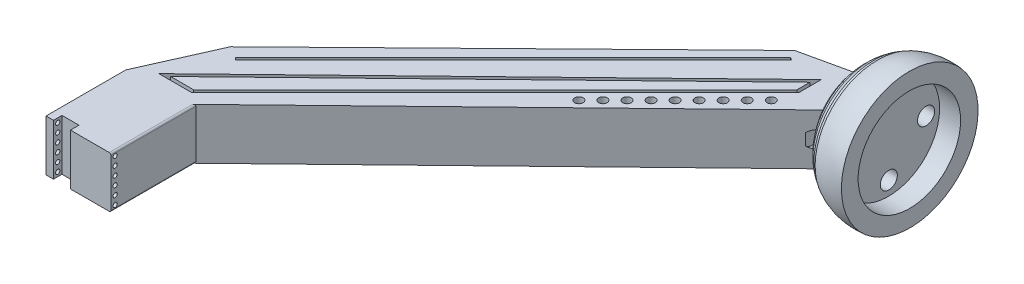
SolidWorks part; units mm, degrees
material "1060 Alloy"
ref_plane "Front Plane" through (0, 0, 0) normal (0, 0, 1) x (1, 0, 0)
ref_plane "Top Plane" through (0, 0, 0) normal (0, 1, 0) x (1, 0, 0)
ref_plane "Right Plane" through (0, 0, 0) normal (1, 0, 0) x (0, 0, -1)
sketch "Sketch1" plane through (0, 0, 0) normal (0, 1, 0) x (1, 0, 0)
  line L0 (-359.7122, -316.6922) -> (-359.7122, -189.6922)
  line L1 (-359.7122, -189.6922) -> (185.2241, 342.9318)
  line L2 (185.2241, 342.9318) -> (213.5101, 342.8041)
  line L3 (213.5101, 342.8041) -> (213.5101, 304.1714)
  line L4 (213.5101, 304.1714) -> (217.8609, 276.2217)
  line L5 (217.8609, 276.2217) -> (-262.803, -189.6922)
  line L6 (-262.803, -189.6922) -> (-262.803, -316.6922)
  line L7 (-262.803, -316.6922) -> (-359.7122, -316.6922)
  dimension "D1" = 762
  dimension "D2" = 127
extrude "Boss-Extrude1" add sketch "Sketch1" along normal blind 76.2
ref_plane "Plane1" through (1.4653, 0, -324.4575) normal (0.0045, 0, -1) x (-1, 0, -0.0045)
sketch "Sketch2" plane through (1.4653, 0, -324.4575) normal (0.0045, 0, -1) x (-1, 0, -0.0045)
  line L0 (-211.9599, 38.1) -> (-386.4485, 38.1) construction
  line L1 (-211.9599, 76.2) -> (-211.9599, 0) construction
sketch "Sketch3" plane through (1.4653, 0, -324.4575) normal (0.0045, 0, -1) x (-1, 0, -0.0045)
  line L0 (-289.3075, 139.7) -> (-289.3075, 38.1)
  line L1 (-211.9599, 38.1) -> (-386.4485, 38.1) construction
  line L2 (-289.3075, 38.1) -> (-185.548, 38.1)
  spline S0 degree 2 poles (-185.548, 38.1) (-211.3385, 147.1791) (-289.3075, 139.7) knots 0 0 0 1 1 1
  dimension "D1" = 101.6
revolve "Revolve1" add sketch "Sketch3" angle 360 about L0 region at (248.1956, 82.1116, -323.3432)
fillet "Fillet1" radius 20.32 1 edges at (192.4111, 35.4411, -342.8994)
fillet "Fillet2" radius 20.32 1 edges at (-359.7122, 38.1, 189.6922)
ref_plane "Plane4" through (308.6083, 0, 1.3937) normal (1, 0, 0.0045) x (0.0045, 0, -1)
sketch "Sketch4" plane through (308.6083, 0, 1.3937) normal (1, 0, 0.0045) x (0.0045, 0, -1)
  circle A0 centre (323.8985, 38.1) radius 76.2
  dimension "D1" = 152.4
extrude "Cut-Extrude1" cut sketch "Sketch4" against normal blind 50.8
ref_plane "Plane5" through (199.644, 0, 0) normal (1, 0, 0) x (0, 0, -1)
sketch "Sketch5" plane through (199.644, 0, 0) normal (1, 0, 0) x (0, 0, -1)
  circle A0 centre (325.0415, 93.4999) radius 12.7
  dimension "D1" = 25.4
extrude "Cut-Extrude2" cut sketch "Sketch5" along normal through all
sketch "Sketch6" plane through (199.644, 0, 0) normal (1, 0, 0) x (0, 0, -1)
  circle A0 centre (323.3573, 38.1) radius 55.4255
  circle A1 centre (378.7828, 38.1) radius 12.7
  circle A2 centre (323.3573, -17.3255) radius 12.7
  circle A3 centre (267.9318, 38.1) radius 12.7
  circle A4 centre (325.0415, 93.4999) radius 12.7 construction
  dimension "D1" = 110.8509
extrude "Cut-Extrude3" cut sketch "Sketch6" along normal through all contours A0 A1 | A0 A3 | A0 A3 | A1 | A2 region at (199.644, 38.1, -383.9023) region at (199.644, 38.1, -273.5754) region at (199.644, 38.1, -262.8123)
ref_plane "Plane6" through (0, 76.2, 0) normal (0, 1, 0) x (1, 0, 0)
sketch "Sketch7" plane through (0, 76.2, 0) normal (0, 1, 0) x (1, 0, 0)
  line L0 (-262.803, -189.6922) -> (212.8674, 271.3814) construction
  circle A0 centre (18.0584, 101.6525) radius 6.35
  circle A1 centre (36.0189, 119.613) radius 6.35
  circle A2 centre (53.9794, 137.5736) radius 6.35
  circle A3 centre (71.9399, 155.5341) radius 6.35
  circle A4 centre (89.9004, 173.4946) radius 6.35
  circle A5 centre (107.861, 191.4551) radius 6.35
  circle A6 centre (125.8215, 209.4156) radius 6.35
  circle A7 centre (143.782, 227.3761) radius 6.35
  circle A8 centre (161.7425, 245.3366) radius 6.35
  dimension "D1" = 12.7
  dimension "D2" = 13.716
  dimension "D3" = 9
extrude "Cut-Extrude5" cut sketch "Sketch7" against normal through all
ref_plane "Plane7" through (0, 76.2, 0) normal (0, 1, 0) x (1, 0, 0)
sketch "Sketch8" plane through (0, 76.2, 0) normal (0, 1, 0) x (1, 0, 0)
  line L0 (-348.5362, -316.6922) -> (-348.5362, -303.9922)
  line L1 (-359.7122, -316.6922) -> (-262.803, -316.6922) construction
  line L2 (-348.5362, -303.9922) -> (-323.1362, -303.9922)
  line L3 (-323.1362, -303.9922) -> (-323.1362, -316.6922)
  line L4 (-323.1362, -316.6922) -> (-348.5362, -316.6922)
  line L5 (-359.7122, -198.2454) -> (-359.7122, -316.6922) construction
  dimension "D1" = 25.4
  dimension "D2" = 12.7
  dimension "D3" = 11.176
extrude "Cut-Extrude6" cut sketch "Sketch8" against normal through all
sketch "Sketch9" plane through (199.644, 0, 0) normal (1, 0, 0) x (0, 0, -1)
  circle A0 centre (324.5589, 37.4496) radius 77.8597
  circle A1 centre (324.5589, 37.4496) radius 84.4013
extrude "Cut-Extrude7" cut sketch "Sketch9" along normal blind 43.18
sketch "Sketch10" plane through (199.644, 0, 0) normal (1, 0, 0) x (0, 0, -1)
  circle A0 centre (325.0474, 38.1) radius 90.2948
  circle A1 centre (325.0474, 38.1) radius 93.6462
extrude "Cut-Extrude8" cut sketch "Sketch10" along normal blind 50.8
sketch "Sketch11" plane through (0, 76.2, 0) normal (0, 1, 0) x (1, 0, 0)
  line L0 (172.325, 309.4891) -> (-330.2511, -177.5829)
  line L1 (-330.2511, -177.5829) -> (-281.2049, -177.5829)
  line L2 (-281.2049, -177.5829) -> (172.325, 275.947)
  line L3 (172.325, 275.947) -> (172.325, 309.4891)
  line L4 (167.245, 278.0512) -> (167.245, 297.4915)
  line L5 (167.245, 297.4915) -> (-317.71, -172.5029)
  line L6 (-317.71, -172.5029) -> (-283.3091, -172.5029)
  line L7 (-283.3091, -172.5029) -> (167.245, 278.0512)
  dimension "D1" = 5.08
extrude "Cut-Extrude10" cut sketch "Sketch11" against normal blind 7.62
ref_plane "Plane8" through (0, 0, 0) normal (0, -1, 0) x (-1, 0, 0)
sketch "Sketch12" plane through (0, 0, 0) normal (0, -1, 0) x (-1, 0, 0)
  line L64 (-174.7165, 323.2482) -> (331.9339, -177.365)
  line L65 (331.9339, -177.365) -> (282.038, -186.0962)
  line L66 (282.038, -186.0962) -> (-183.914, 287.2831)
  line L67 (-183.914, 287.2831) -> (-174.7165, 323.2482)
  line L68 (-178.2819, 288.8029) -> (-171.9887, 313.4114)
  line L69 (-171.9887, 313.4114) -> (321.3595, -174.0582)
  line L70 (321.3595, -174.0582) -> (283.7883, -180.6327)
  line L71 (283.7883, -180.6327) -> (-178.2819, 288.8029)
  dimension "D1" = 5.08
extrude "Cut-Extrude11" cut sketch "Sketch12" against normal blind 7.62
fillet "Fillet7" radius 2.54 1 edges at (-262.803, 76.2, 253.1922)
fillet "Fillet8" radius 2.54 1 edges at (-262.803, 0, 253.1922)
sketch "Sketch15" plane through (-80.9252, 0, -82.7959) normal (-0.699, 0, -0.7151) x (-0.7151, 0, 0.699)
  line L0 (-372.1642, 76.2) -> (-372.1642, 0) construction
  line L1 (-372.1642, 76.2) -> (381.2827, 76.2) construction
  line L2 (381.2827, 0) -> (381.2827, 76.2) construction
  line L3 (-372.1642, 0) -> (381.2827, 0) construction
  line L4 (-372.1642, 76.2) -> (-372.1642, 0)
  line L5 (-372.1642, 76.2) -> (381.2827, 76.2)
  line L6 (381.2827, 0) -> (381.2827, 76.2)
  line L7 (-372.1642, 0) -> (381.2827, 0)
extrude "Boss-Extrude2" add sketch "Sketch15" along normal blind 38.1
fillet "Fillet10" radius 40.64 1 edges at (158.5929, 38.1, -370.1786)
fillet "Fillet11" radius 40.64 1 edges at (-380.2267, 38.1, 156.4669)
sketch "Sketch17" plane through (-107.5564, 0, -110.0427) normal (-0.699, 0, -0.7151) x (-0.7151, 0, 0.699)
  line L0 (340.7221, 76.2) -> (-331.6036, 76.2) construction
  line L1 (-323.5295, 55.88) -> (57.4705, 55.88)
  line L2 (-323.5295, 55.88) -> (-323.5295, 60.96)
  line L3 (-323.5295, 60.96) -> (57.4705, 60.96)
  line L4 (57.4705, 55.88) -> (57.4705, 60.96)
  line L5 (-323.5295, 15.24) -> (57.4705, 15.24)
  line L6 (-323.5295, 15.24) -> (-323.5295, 20.32)
  line L7 (-323.5295, 20.32) -> (57.4705, 20.32)
  line L8 (57.4705, 15.24) -> (57.4705, 20.32)
  line L9 (-331.6036, 0) -> (340.7221, 0) construction
  dimension "D1" = 5.08
  dimension "D2" = 5.08
  dimension "D3" = 381
  dimension "D4" = 381
  dimension "D5" = 15.24
  dimension "D6" = 15.24
extrude "Cut-Extrude14" cut sketch "Sketch17" against normal blind 0.508
sketch "Sketch18" plane through (0, 76.2, 0) normal (0, 1, 0) x (1, 0, 0)
  line L0 (-297.9829, -58.9871) -> (-372.1047, -225.3494)
  line L1 (-372.1047, -225.3494) -> (-395.1648, -58.9871)
  line L2 (-395.1648, -58.9871) -> (-297.9829, -58.9871)
  line L3 (-297.9829, -58.9871) -> (-299.081, -58.9871)
  line M17 (129.5865, 341.8276) -> (-351.2203, -128.1158)
  arc M18 (-351.2203, -128.1158) -> (-353.5955, -183.7137) centre (-322.8137, -157.1791) ccw
  arc M19 (-353.5955, -183.7137) -> (-359.7122, -198.2454) centre (-339.3922, -198.2454) ccw
extrude "Cut-Extrude15" cut sketch "Sketch18" against normal through all contours L2 L1 L0 M19 M18 M17 | L0 M17 M18 M19 region at (-357.5935, 76.2, 108.5211) region at (-344.0436, 76.2, 140.489)
sketch "Sketch19" plane through (0, 76.2, 0) normal (0, 1, 0) x (1, 0, 0)
  line L0 (185.2241, 342.9318) -> (57.4565, 314.5117)
  line L1 (57.4565, 314.5117) -> (137.4768, 418.5381)
  line L2 (137.4768, 418.5381) -> (185.2241, 342.9318)
  arc M35 (185.2241, 342.9318) -> (129.5865, 341.8276) centre (157.9931, 312.7643) ccw
  line M36 (129.5865, 341.8276) -> (-311.4743, -89.2679)
extrude "Cut-Extrude16" cut sketch "Sketch19" against normal through all contours L2 L1 L0 M36 M35 | L0 M35 M36 region at (122.5761, 76.2, -361.5313) region at (150.4405, 76.2, -342.2239)
sketch "Sketch20" plane through (0, 76.2, 0) normal (0, 1, 0) x (1, 0, 0)
  line L0 (120.584, 315.2892) -> (-294.1927, -99.4875)
  line L1 (-294.1927, -99.4875) -> (-290.7829, -102.8974)
  line L2 (-290.7829, -102.8974) -> (124.5729, 312.4584)
  line L3 (120.584, 315.2892) -> (124.5729, 312.4584)
extrude "Cut-Extrude17" cut sketch "Sketch20" against normal through all
sketch "Sketch21" plane through (-359.7122, 0, 0) normal (-1, 0, 0) x (0, 0, 1)
  line L0 (316.6922, 76.2) -> (316.6922, 0) construction
  line L1 (198.2454, 76.2) -> (316.6922, 76.2) construction
  line L2 (198.2454, 0) -> (316.6922, 0) construction
  circle A0 centre (310.3422, 69.85) radius 3.175
  circle A1 centre (310.3422, 57.15) radius 3.175
  circle A2 centre (310.3422, 44.45) radius 3.175
  circle A3 centre (310.3422, 6.35) radius 3.2044
  circle A4 centre (310.3422, 19.05) radius 3.2044
  circle A5 centre (310.3422, 31.75) radius 3.2044
  dimension "D3" = 6.35
  dimension "D5" = 6.4087
  dimension "D1" = 6.35
  dimension "D2" = 6.35
  dimension "D6" = 6.35
  dimension "D7" = 6.35
  dimension "D4" = 3
  dimension "D8" = 3
extrude "Cut-Extrude18" cut sketch "Sketch21" against normal through all
sketch "Sketch22" plane through (-63.9517, 0, -287.5061) normal (-0.2171, 0, -0.9761) x (-0.9761, 0, 0.2171)
  line L0 (-273.3366, 59.9094) -> (-332.9975, 45.9609) construction
  dimension "D1" = 59.6609
